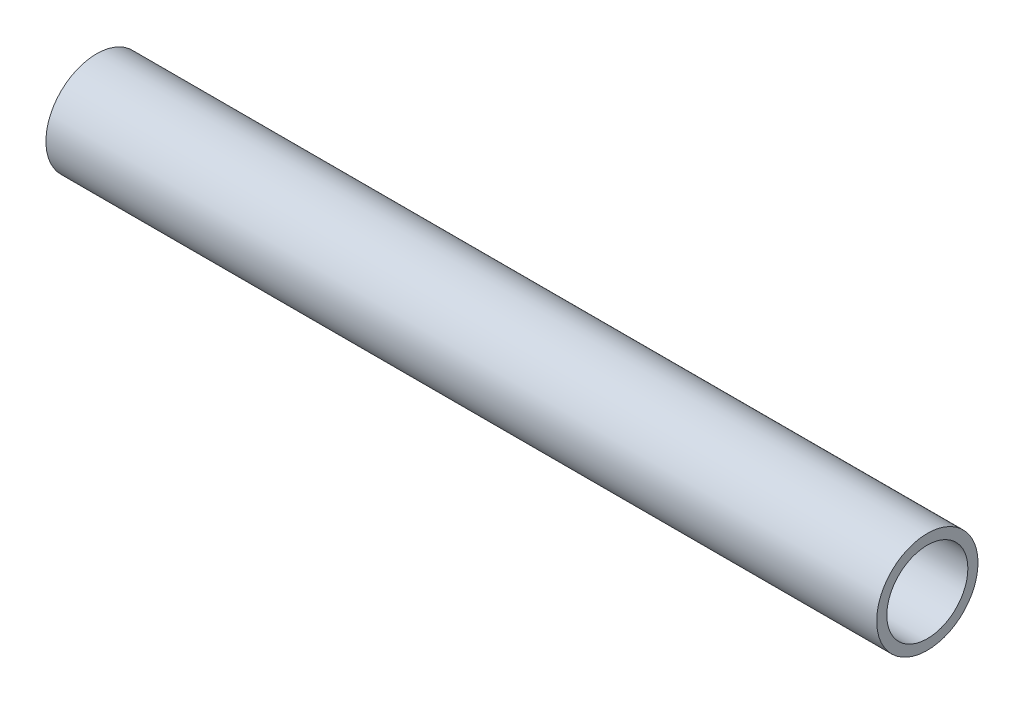
SolidWorks part; units mm, degrees
material "PC High Viscosity"
ref_plane "Front Plane" through (0, 0, 0) normal (0, 0, 1) x (1, 0, 0)
ref_plane "Top Plane" through (0, 0, 0) normal (0, 1, 0) x (1, 0, 0)
ref_plane "Right Plane" through (0, 0, 0) normal (1, 0, 0) x (0, 0, -1)
sketch "Sketch1" plane through (0, 0, 0) normal (1, 0, 0) x (0, 0, -1)
  circle A0 centre (0, 0) radius 15.875
  dimension "D1" = 31.75
extrude "Extrude-Thin1" add sketch "Sketch1" along normal mid plane 260.3182 thin thin type one direction reverse wall 3.175
